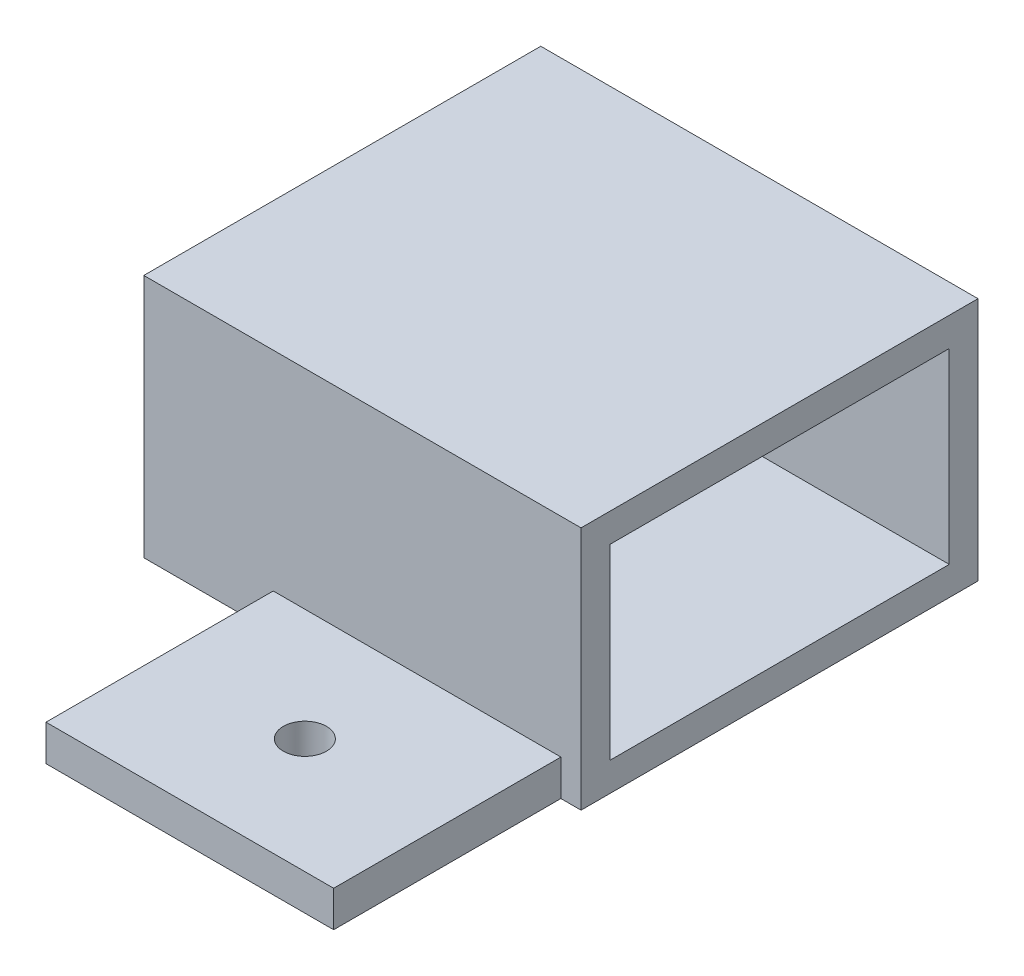
SolidWorks part; units mm, degrees
ref_plane "Front Plane" through (0, 0, 0) normal (0, 0, 1) x (1, 0, 0)
ref_plane "Top Plane" through (0, 0, 0) normal (0, 1, 0) x (1, 0, 0)
ref_plane "Right Plane" through (0, 0, 0) normal (1, 0, 0) x (0, 0, -1)
ref_plane "PZ_m34_000" through (0, 0, -34) normal (0, 0, 1) x (1, 0, 0)
sketch "S_box1" plane through (0, 0, -34) normal (0, 0, 1) x (1, 0, 0)
  line L0 (-10, 1.5) -> (10, 1.5)
  line L1 (10, 1.5) -> (10, 4)
  line L2 (10, 4) -> (-10, 4)
  line L3 (-10, 4) -> (-10, 1.5)
  dimension "P1" = 10
  dimension "P2" = 1.5
  dimension "P3" = 10
  dimension "P4" = 1.5
  dimension "P5" = 10
  dimension "P6" = 4
  dimension "P7" = 10
  dimension "P8" = 4
extrude "Boss_1" add sketch "S_box1" along normal blind 42
ref_plane "PZ_m35_400" through (0, 0, -35.4) normal (0, 0, 1) x (1, 0, 0)
sketch "S_box2" plane through (0, 0, -35.4) normal (0, 0, 1) x (1, 0, 0)
  line L0 (-19, 1.5) -> (11.4, 1.5)
  line L1 (11.4, 1.5) -> (11.4, 18.5)
  line L2 (11.4, 18.5) -> (-19, 18.5)
  line L3 (-19, 18.5) -> (-19, 1.5)
  dimension "P1" = 19
  dimension "P2" = 1.5
  dimension "P3" = 11.4
  dimension "P4" = 1.5
  dimension "P5" = 11.4
  dimension "P6" = 18.5
  dimension "P7" = 19
  dimension "P8" = 18.5
extrude "Boss_2" add sketch "S_box2" along normal blind 27.6
ref_plane "PZ_m33_400" through (0, 0, -33.4) normal (0, 0, 1) x (1, 0, 0)
sketch "S_cut3" plane through (0, 0, -33.4) normal (0, 0, 1) x (1, 0, 0)
  line L0 (-19.1, 3.5) -> (11.5, 3.5)
  line L1 (11.5, 3.5) -> (11.5, 16.5)
  line L2 (11.5, 16.5) -> (-19.1, 16.5)
  line L3 (-19.1, 16.5) -> (-19.1, 3.5)
  dimension "P1" = 19.1
  dimension "P2" = 3.5
  dimension "P3" = 11.5
  dimension "P4" = 3.5
  dimension "P5" = 11.5
  dimension "P6" = 16.5
  dimension "P7" = 19.1
  dimension "P8" = 16.5
extrude "Pocket_3" cut sketch "S_cut3" along normal blind 23.6
ref_plane "PY_p1_400" through (0, 1.4, 0) normal (0, 1, 0) x (1, 0, 0)
sketch "S_hole4" plane through (0, 1.4, 0) normal (0, 1, 0) x (1, 0, 0)
  circle A0 centre (0, 0) radius 1.5
  dimension "D1_S_hole4" = 3
extrude "Hole_4" cut sketch "S_hole4" along normal blind 2.7
equation "\"plate_t\" = 3"
equation "\"clearance\" = 0.4"
